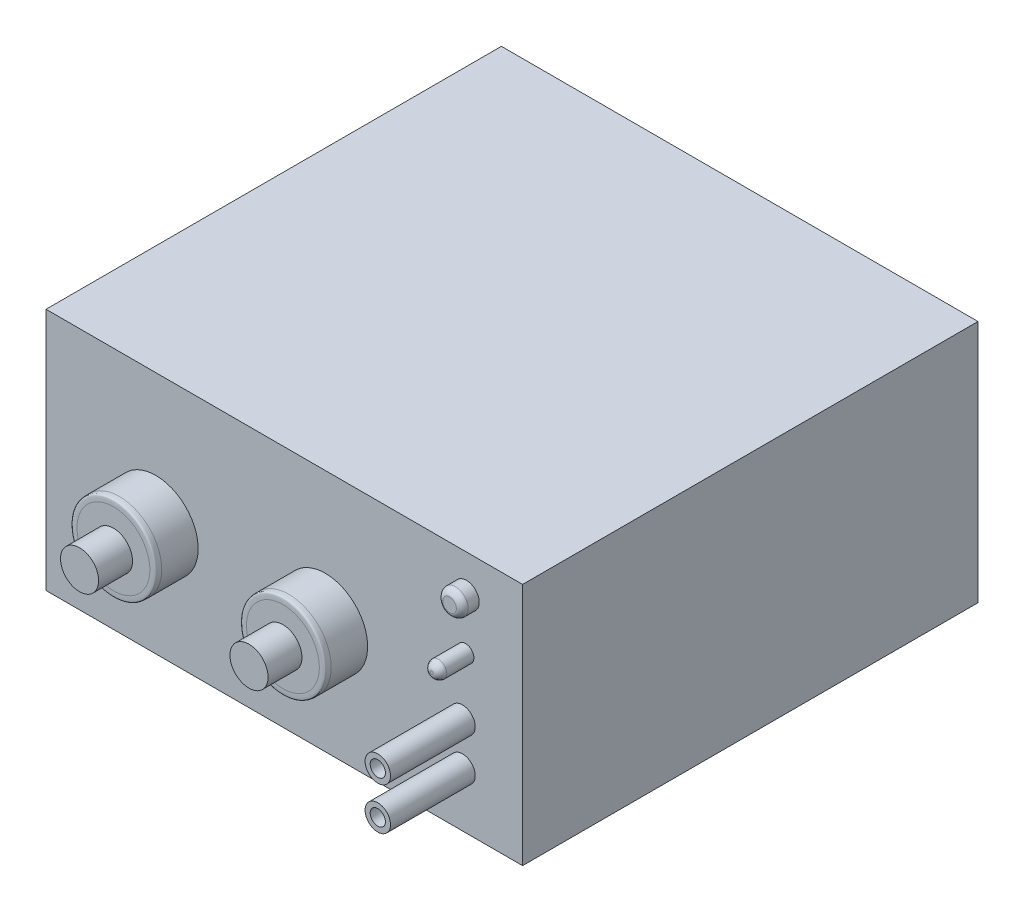
SolidWorks part; units mm, degrees
ref_plane "Front Plane" through (0, 0, 0) normal (0, 0, 1) x (1, 0, 0)
ref_plane "Top Plane" through (0, 0, 0) normal (0, 1, 0) x (1, 0, 0)
ref_plane "Right Plane" through (0, 0, 0) normal (1, 0, 0) x (0, 0, -1)
sketch "Sketch1" plane through (0, 0, 0) normal (0, 1, 0) x (1, 0, 0)
  line L1 (-71.4375, -68.2625) -> (71.4375, -68.2625)
  line L2 (-71.4375, -68.2625) -> (-71.4375, 68.2625)
  line L3 (-71.4375, 68.2625) -> (71.4375, 68.2625)
  line L4 (71.4375, -68.2625) -> (71.4375, 68.2625)
  line L5 (-71.4375, -68.2625) -> (71.4375, 68.2625) construction
  line L6 (-71.4375, 68.2625) -> (71.4375, -68.2625) construction
  point P0 (0, 0)
  dimension "D1" = 142.875
  dimension "D2" = 136.525
extrude "Boss-Extrude1" add sketch "Sketch1" along normal blind 73.025
sketch "Sketch2" plane through (0, 0, 68.2625) normal (0, 0, 1) x (1, 0, 0)
  circle A0 centre (-38.5167, 33.6502) radius 12.7
  dimension "D1" = 25.4
extrude "Boss-Extrude2" add sketch "Sketch2" along normal blind 12.7
fillet "Fillet2" radius 1.778 1 edges at (-25.8167, 33.6502, 80.9625) conic radius 0.254
sketch "Sketch3" plane through (0, 0, 68.2625) normal (0, 0, 1) x (1, 0, 0)
  circle A0 centre (-38.5167, 33.2906) radius 5.715
  point P2 (0, 0)
  point P3 (-38.5167, 33.2906)
  dimension "D1" = 11.43
extrude "Boss-Extrude3" add sketch "Sketch3" along normal blind 22.86 contours A0
pattern_linear "LPattern1" count 2 spacing 50.8 along (1, 0, 0) of "Boss-Extrude2"
fillet "Fillet3" radius 1.778 1 edges at (24.9833, 33.6502, 80.9625) conic radius 0.254
sketch "Sketch5" plane through (0, 0, 80.9625) normal (0, 0, 1) x (1, 0, 0)
  circle A0 centre (12.2833, 33.6502) radius 5.715
  dimension "D1" = 11.43
extrude "Boss-Extrude4" add sketch "Sketch5" along normal blind 10.16
sketch "Sketch6" plane through (0, 0, 68.2625) normal (0, 0, 1) x (1, 0, 0)
  circle A0 centre (54.6276, 61.8578) radius 3.81
  dimension "D1" = 7.62
extrude "Boss-Extrude5" add sketch "Sketch6" along normal blind 5.08
fillet "Fillet4" radius 1.778 1 edges at (58.4376, 61.8578, 73.3425) conic radius 2.794
sketch "Sketch7" plane through (0, 0, 68.2625) normal (0, 0, 1) x (1, 0, 0)
  circle A0 centre (54.3383, 46.6192) radius 2.5
  dimension "D1" = 5
extrude "Boss-Extrude6" add sketch "Sketch7" along normal blind 10.16
fillet "Fillet5" radius 2.032 1 edges at (56.8383, 46.6192, 78.4225) conic radius 2.54
sketch "Sketch9" plane through (0, 0, 68.2625) normal (0, 0, 1) x (1, 0, 0)
  circle A0 centre (53.4316, 28.9298) radius 3.81
  dimension "D1" = 7.62
extrude "Boss-Extrude7" add sketch "Sketch9" along normal blind 25.4
sketch "Sketch10" plane through (0, 0, 93.6625) normal (0, 0, 1) x (1, 0, 0)
  circle A0 centre (53.4316, 28.9298) radius 2.286
  circle A1 centre (53.4316, 28.9298) radius 3.81 construction
  dimension "D1" = 1.524
extrude "Cut-Extrude1" cut sketch "Sketch10" against normal blind 25.4
pattern_linear "LPattern2" count 2 spacing 12.7 along (0, -1, 0) of "Boss-Extrude7"
sketch "Sketch11" plane through (0, 0, 93.6625) normal (0, 0, 1) x (1, 0, 0)
  circle A0 centre (53.4316, 16.2298) radius 2.286
  circle A1 centre (53.4316, 16.2298) radius 3.81 construction
  dimension "D1" = 1.524
extrude "Cut-Extrude2" cut sketch "Sketch11" against normal blind 25.4
